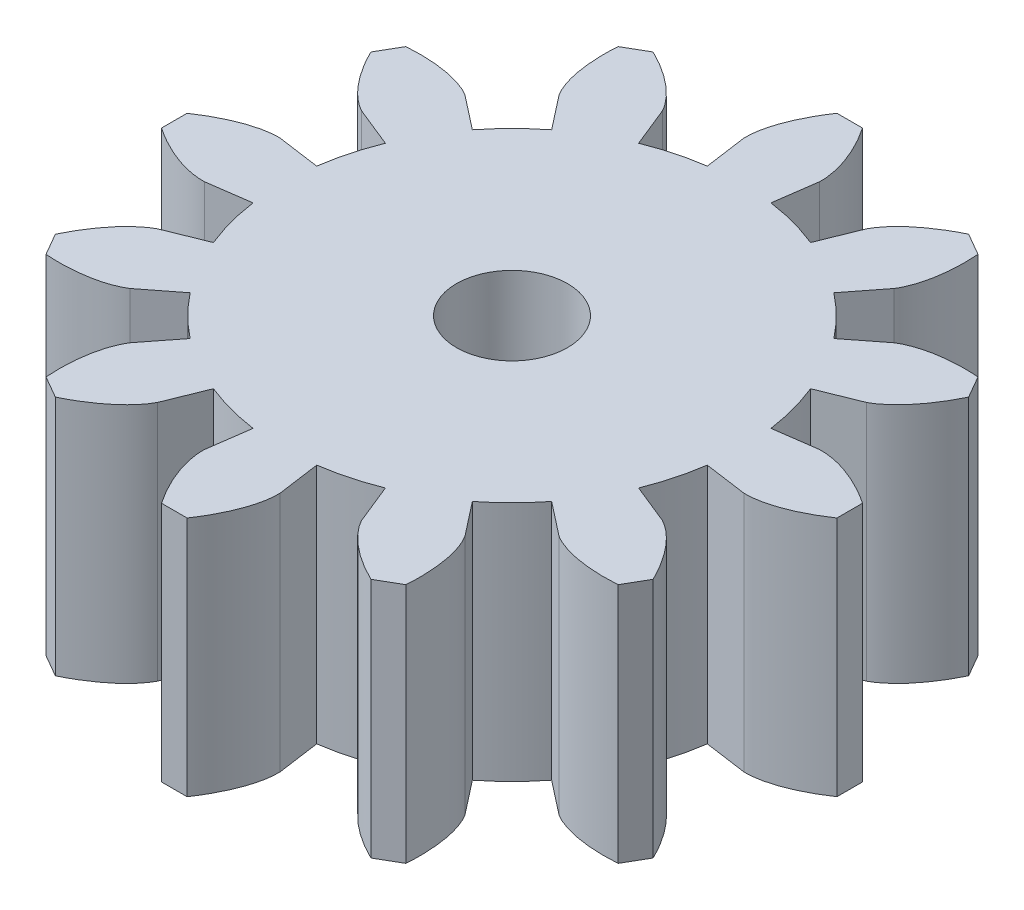
SolidWorks part; units mm, degrees
ref_plane "Front Plane" through (0, 0, 0) normal (0, 0, 1) x (1, 0, 0)
ref_plane "Top Plane" through (0, 0, 0) normal (0, 1, 0) x (1, 0, 0)
ref_plane "Right Plane" through (0, 0, 0) normal (1, 0, 0) x (0, 0, -1)
ref_plane "Plane1" through (0, -5, 0) normal (0, -1, 0) x (1, 0, 0)
sketch "Sketch1" plane through (0, -5, 0) normal (0, -1, 0) x (1, 0, 0)
  line L0 (3.7441, -2.923) -> (4.4442, -3.4696)
  line L1 (5.9256, -3.7266) -> (6.1901, -3.2684)
  line L2 (5.2268, -2.114) -> (4.4035, -1.781)
  line L3 (4.704, -0.6593) -> (5.5836, -0.7826)
  line L4 (6.995, -0.2646) -> (6.995, 0.2646)
  line L5 (5.5836, 0.7826) -> (4.704, 0.6593)
  line L6 (4.4035, 1.781) -> (5.2268, 2.114)
  line L7 (6.1901, 3.2684) -> (5.9256, 3.7266)
  line L8 (4.4442, 3.4696) -> (3.7441, 2.923)
  line L9 (2.923, 3.7441) -> (3.4696, 4.4442)
  line L10 (3.7266, 5.9256) -> (3.2684, 6.1901)
  line L11 (2.114, 5.2268) -> (1.781, 4.4035)
  line L12 (0.6593, 4.704) -> (0.7826, 5.5836)
  line L13 (0.2646, 6.995) -> (-0.2646, 6.995)
  line L14 (-0.7826, 5.5836) -> (-0.6593, 4.704)
  line L15 (-1.781, 4.4035) -> (-2.114, 5.2268)
  line L16 (-3.2684, 6.1901) -> (-3.7266, 5.9256)
  line L17 (-3.4696, 4.4442) -> (-2.923, 3.7441)
  line L18 (-3.7441, 2.923) -> (-4.4442, 3.4696)
  line L19 (-5.9256, 3.7266) -> (-6.1901, 3.2684)
  line L20 (-5.2268, 2.114) -> (-4.4035, 1.781)
  line L21 (-4.704, 0.6593) -> (-5.5836, 0.7826)
  line L22 (-6.995, 0.2646) -> (-6.995, -0.2646)
  line L23 (-5.5836, -0.7826) -> (-4.704, -0.6593)
  line L24 (-4.4035, -1.781) -> (-5.2268, -2.114)
  line L25 (-6.1901, -3.2684) -> (-5.9256, -3.7266)
  line L26 (-4.4442, -3.4696) -> (-3.7441, -2.923)
  line L27 (-2.923, -3.7441) -> (-3.4696, -4.4442)
  line L28 (-3.7266, -5.9256) -> (-3.2684, -6.1901)
  line L29 (-2.114, -5.2268) -> (-1.781, -4.4035)
  line L30 (-0.6593, -4.704) -> (-0.7826, -5.5836)
  line L31 (-0.2646, -6.995) -> (0.2646, -6.995)
  line L32 (0.7826, -5.5836) -> (0.6593, -4.704)
  line L33 (1.781, -4.4035) -> (2.114, -5.2268)
  line L34 (3.2684, -6.1901) -> (3.7266, -5.9256)
  line L35 (3.4696, -4.4442) -> (2.923, -3.7441)
  arc A0 (2.923, -3.7441) -> (3.7441, -2.923) centre (0, 0) ccw
  arc A1 (4.4035, -1.781) -> (4.704, -0.6593) centre (0, 0) ccw
  arc A2 (4.704, 0.6593) -> (4.4035, 1.781) centre (0, 0) ccw
  arc A3 (3.7441, 2.923) -> (2.923, 3.7441) centre (0, 0) ccw
  arc A4 (1.781, 4.4035) -> (0.6593, 4.704) centre (0, 0) ccw
  arc A5 (-0.6593, 4.704) -> (-1.781, 4.4035) centre (0, 0) ccw
  arc A6 (-2.923, 3.7441) -> (-3.7441, 2.923) centre (0, 0) ccw
  arc A7 (-4.4035, 1.781) -> (-4.704, 0.6593) centre (0, 0) ccw
  arc A8 (-4.704, -0.6593) -> (-4.4035, -1.781) centre (0, 0) ccw
  arc A9 (-3.7441, -2.923) -> (-2.923, -3.7441) centre (0, 0) ccw
  arc A10 (-1.781, -4.4035) -> (-0.6593, -4.704) centre (0, 0) ccw
  arc A11 (0.6593, -4.704) -> (1.781, -4.4035) centre (0, 0) ccw
  ellipse E0 centre (5.8654, -2.9875) end of major axis (7.546, -2.8631) minor radius 0.7415 (4.4442, -3.4696) -> (5.9256, -3.7266) ccw
  ellipse E1 centre (5.5279, -3.5513) end of major axis (6.2585, -5.0325) minor radius 0.7192 (6.1901, -3.2684) -> (5.2268, -2.114) ccw
  ellipse E2 centre (6.5733, 0.3454) end of major axis (7.9666, 1.2935) minor radius 0.7415 (5.5836, -0.7826) -> (6.995, -0.2646) ccw
  ellipse E3 centre (6.563, -0.3115) end of major axis (7.9362, -1.229) minor radius 0.7192 (6.995, 0.2646) -> (5.5836, 0.7826) ccw
  ellipse E4 centre (5.5199, 3.5858) end of major axis (4.7874, 2.068) minor radius 0.7415 (5.2268, 2.114) -> (6.1901, 3.2684) ccw
  ellipse E5 centre (5.8394, 3.0117) end of major axis (7.4875, 2.9038) minor radius 0.7192 (5.9256, 3.7266) -> (4.4442, 3.4696) ccw
  ellipse E6 centre (2.9875, 5.8654) end of major axis (3.112, 4.1847) minor radius 0.7415 (3.4696, 4.4442) -> (3.7266, 5.9256) ccw
  ellipse E7 centre (3.5513, 5.5279) end of major axis (5.0325, 6.2585) minor radius 0.7192 (3.2684, 6.1901) -> (2.114, 5.2268) ccw
  ellipse E8 centre (-0.3454, 6.5733) end of major axis (0.6027, 5.18) minor radius 0.7415 (0.7826, 5.5836) -> (0.2646, 6.995) ccw
  ellipse E9 centre (0.3115, 6.563) end of major axis (-0.606, 5.1897) minor radius 0.7192 (-0.2646, 6.995) -> (-0.7826, 5.5836) ccw
  ellipse E10 centre (-3.5858, 5.5199) end of major axis (-2.068, 4.7874) minor radius 0.7415 (-2.114, 5.2268) -> (-3.2684, 6.1901) ccw
  ellipse E11 centre (-3.0117, 5.8394) end of major axis (-3.1197, 4.1914) minor radius 0.7192 (-3.7266, 5.9256) -> (-3.4696, 4.4442) ccw
  ellipse E12 centre (-5.8654, 2.9875) end of major axis (-4.1847, 3.112) minor radius 0.7415 (-4.4442, 3.4696) -> (-5.9256, 3.7266) ccw
  ellipse E13 centre (-5.5279, 3.5513) end of major axis (-4.7974, 2.07) minor radius 0.7192 (-6.1901, 3.2684) -> (-5.2268, 2.114) ccw
  ellipse E14 centre (-6.5733, -0.3454) end of major axis (-5.18, 0.6027) minor radius 0.7415 (-5.5836, 0.7826) -> (-6.995, 0.2646) ccw
  ellipse E15 centre (-6.563, 0.3115) end of major axis (-5.1897, -0.606) minor radius 0.7192 (-6.995, -0.2646) -> (-5.5836, -0.7826) ccw
  ellipse E16 centre (-5.5199, -3.5858) end of major axis (-6.2525, -5.1035) minor radius 0.7415 (-5.2268, -2.114) -> (-6.1901, -3.2684) ccw
  ellipse E17 centre (-5.8394, -3.0117) end of major axis (-4.1914, -3.1197) minor radius 0.7192 (-5.9256, -3.7266) -> (-4.4442, -3.4696) ccw
  ellipse E18 centre (-2.9875, -5.8654) end of major axis (-2.8631, -7.546) minor radius 0.7415 (-3.4696, -4.4442) -> (-3.7266, -5.9256) ccw
  ellipse E19 centre (-3.5513, -5.5279) end of major axis (-5.0325, -6.2585) minor radius 0.7192 (-3.2684, -6.1901) -> (-2.114, -5.2268) ccw
  ellipse E20 centre (0.3454, -6.5733) end of major axis (1.2935, -7.9666) minor radius 0.7415 (-0.7826, -5.5836) -> (-0.2646, -6.995) ccw
  ellipse E21 centre (-0.3115, -6.563) end of major axis (-1.229, -7.9362) minor radius 0.7192 (0.2646, -6.995) -> (0.7826, -5.5836) ccw
  ellipse E22 centre (3.5858, -5.5199) end of major axis (5.1035, -6.2525) minor radius 0.7415 (2.114, -5.2268) -> (3.2684, -6.1901) ccw
  ellipse E23 centre (3.0117, -5.8394) end of major axis (2.9038, -7.4875) minor radius 0.7192 (3.7266, -5.9256) -> (3.4696, -4.4442) ccw
  point P4 (5.8654, -2.9875)
  point P5 (7.546, -2.8631)
  point P6 (5.9201, -3.727)
  point P7 (4.4442, -3.4696)
  point P8 (5.9256, -3.7266)
  point P9 (5.1439, -3.7018)
  point P10 (6.5868, -2.2732)
  point P18 (5.5279, -3.5513)
  point P19 (6.173, -3.2331)
  point P20 (6.2585, -5.0325)
  point P21 (6.1901, -3.2684)
  point P22 (5.2268, -2.114)
  point P23 (5.7778, -2.6038)
  point P24 (5.2781, -4.4987)
  point P34 (6.5733, 0.3454)
  point P35 (7.9666, 1.2935)
  point P36 (6.9905, -0.2677)
  point P37 (5.5836, -0.7826)
  point P38 (6.995, -0.2646)
  point P39 (6.3057, -0.6339)
  point P40 (6.8409, 1.3247)
  point P48 (6.563, -0.3115)
  point P49 (7.9362, -1.229)
  point P50 (6.1634, -0.9095)
  point P51 (6.995, 0.2646)
  point P52 (5.5836, 0.7826)
  point P53 (6.3057, 0.6339)
  point P54 (6.8203, -1.2569)
  point P64 (5.5199, 3.5858)
  point P65 (6.1878, 3.2634)
  point P66 (4.7874, 2.068)
  point P67 (5.2268, 2.114)
  point P68 (6.1901, 3.2684)
  point P69 (5.7778, 2.6038)
  point P70 (5.2621, 4.5677)
  point P78 (5.8394, 3.0117)
  point P79 (7.4875, 2.9038)
  point P80 (5.7924, 2.294)
  point P81 (5.9256, 3.7266)
  point P82 (4.4442, 3.4696)
  point P83 (5.1439, 3.7018)
  point P84 (6.535, 2.3216)
  point P94 (2.9875, 5.8654)
  point P95 (3.727, 5.9201)
  point P96 (3.112, 4.1847)
  point P97 (3.4696, 4.4442)
  point P98 (3.7266, 5.9256)
  point P99 (3.7018, 5.1439)
  point P100 (2.2732, 6.5868)
  point P108 (3.5513, 5.5279)
  point P109 (5.0325, 6.2585)
  point P110 (3.8694, 4.8829)
  point P111 (3.2684, 6.1901)
  point P112 (2.114, 5.2268)
  point P113 (2.6038, 5.7778)
  point P114 (4.4987, 5.2781)
  point P124 (-0.3454, 6.5733)
  point P125 (0.2677, 6.9905)
  point P126 (0.6027, 5.18)
  point P127 (0.7826, 5.5836)
  point P128 (0.2646, 6.995)
  point P129 (0.6339, 6.3057)
  point P130 (-1.3247, 6.8409)
  point P138 (0.3115, 6.563)
  point P139 (0.9095, 6.1634)
  point P140 (-0.606, 5.1897)
  point P141 (-0.2646, 6.995)
  point P142 (-0.7826, 5.5836)
  point P143 (-0.6339, 6.3057)
  point P144 (1.2569, 6.8203)
  point P154 (-3.5858, 5.5199)
  point P155 (-2.068, 4.7874)
  point P156 (-3.9081, 4.8521)
  point P157 (-2.114, 5.2268)
  point P158 (-3.2684, 6.1901)
  point P159 (-2.6038, 5.7778)
  point P160 (-4.5677, 5.2621)
  point P168 (-3.0117, 5.8394)
  point P169 (-2.294, 5.7924)
  point P170 (-3.1197, 4.1914)
  point P171 (-3.7266, 5.9256)
  point P172 (-3.4696, 4.4442)
  point P173 (-3.7018, 5.1439)
  point P174 (-2.3216, 6.535)
  point P184 (-5.8654, 2.9875)
  point P185 (-4.1847, 3.112)
  point P186 (-5.8106, 2.248)
  point P187 (-4.4442, 3.4696)
  point P188 (-5.9256, 3.7266)
  point P189 (-5.1439, 3.7018)
  point P190 (-6.5868, 2.2732)
  point P198 (-5.5279, 3.5513)
  point P199 (-4.8829, 3.8694)
  point P200 (-4.7974, 2.07)
  point P201 (-6.1901, 3.2684)
  point P202 (-5.2268, 2.114)
  point P203 (-5.7778, 2.6038)
  point P204 (-5.2781, 4.4987)
  point P214 (-6.5733, -0.3454)
  point P215 (-5.18, 0.6027)
  point P216 (-6.1561, -0.9585)
  point P217 (-5.5836, 0.7826)
  point P218 (-6.995, 0.2646)
  point P219 (-6.3057, 0.6339)
  point P220 (-6.8409, -1.3247)
  point P228 (-6.563, 0.3115)
  point P229 (-5.1897, -0.606)
  point P230 (-6.9625, -0.2865)
  point P231 (-6.995, -0.2646)
  point P232 (-5.5836, -0.7826)
  point P233 (-6.3057, -0.6339)
  point P234 (-6.8203, 1.2569)
  point P244 (-5.5199, -3.5858)
  point P245 (-4.8521, -3.9081)
  point P246 (-6.2525, -5.1035)
  point P247 (-5.2268, -2.114)
  point P248 (-6.1901, -3.2684)
  point P249 (-5.7778, -2.6038)
  point P250 (-5.2621, -4.5677)
  point P258 (-5.8394, -3.0117)
  point P259 (-4.1914, -3.1197)
  point P260 (-5.8865, -3.7294)
  point P261 (-5.9256, -3.7266)
  point P262 (-4.4442, -3.4696)
  point P263 (-5.1439, -3.7018)
  point P264 (-6.535, -2.3216)
  point P274 (-2.9875, -5.8654)
  point P275 (-2.248, -5.8106)
  point P276 (-2.8631, -7.546)
  point P277 (-3.4696, -4.4442)
  point P278 (-3.7266, -5.9256)
  point P279 (-3.7018, -5.1439)
  point P280 (-2.2732, -6.5868)
  point P288 (-3.5513, -5.5279)
  point P289 (-2.07, -4.7974)
  point P290 (-3.2331, -6.173)
  point P291 (-3.2684, -6.1901)
  point P292 (-2.114, -5.2268)
  point P293 (-2.6038, -5.7778)
  point P294 (-4.4987, -5.2781)
  point P304 (0.3454, -6.5733)
  point P305 (0.9585, -6.1561)
  point P306 (1.2935, -7.9666)
  point P307 (-0.7826, -5.5836)
  point P308 (-0.2646, -6.995)
  point P309 (-0.6339, -6.3057)
  point P310 (1.3247, -6.8409)
  point P318 (-0.3115, -6.563)
  point P319 (0.2865, -6.9625)
  point P320 (-1.229, -7.9362)
  point P321 (0.2646, -6.995)
  point P322 (0.7826, -5.5836)
  point P323 (0.6339, -6.3057)
  point P324 (-1.2569, -6.8203)
  point P334 (3.5858, -5.5199)
  point P335 (5.1035, -6.2525)
  point P336 (3.2634, -6.1878)
  point P337 (2.114, -5.2268)
  point P338 (3.2684, -6.1901)
  point P339 (2.6038, -5.7778)
  point P340 (4.5677, -5.2621)
  point P348 (3.0117, -5.8394)
  point P349 (3.7294, -5.8865)
  point P350 (2.9038, -7.4875)
  point P351 (3.7266, -5.9256)
  point P352 (3.4696, -4.4442)
  point P353 (3.7018, -5.1439)
  point P354 (2.3216, -6.535)
extrude "Boss-Extrude1" add sketch "Sketch1" against normal blind 5
sketch "Sketch2" plane through (0, 0, 0) normal (0, 1, 0) x (1, 0, 0)
  circle A0 centre (0, 0) radius 1.15
  dimension "D1" = 2.3
extrude "Cut-Extrude1" cut sketch "Sketch2" against normal through all both and the other way through all
